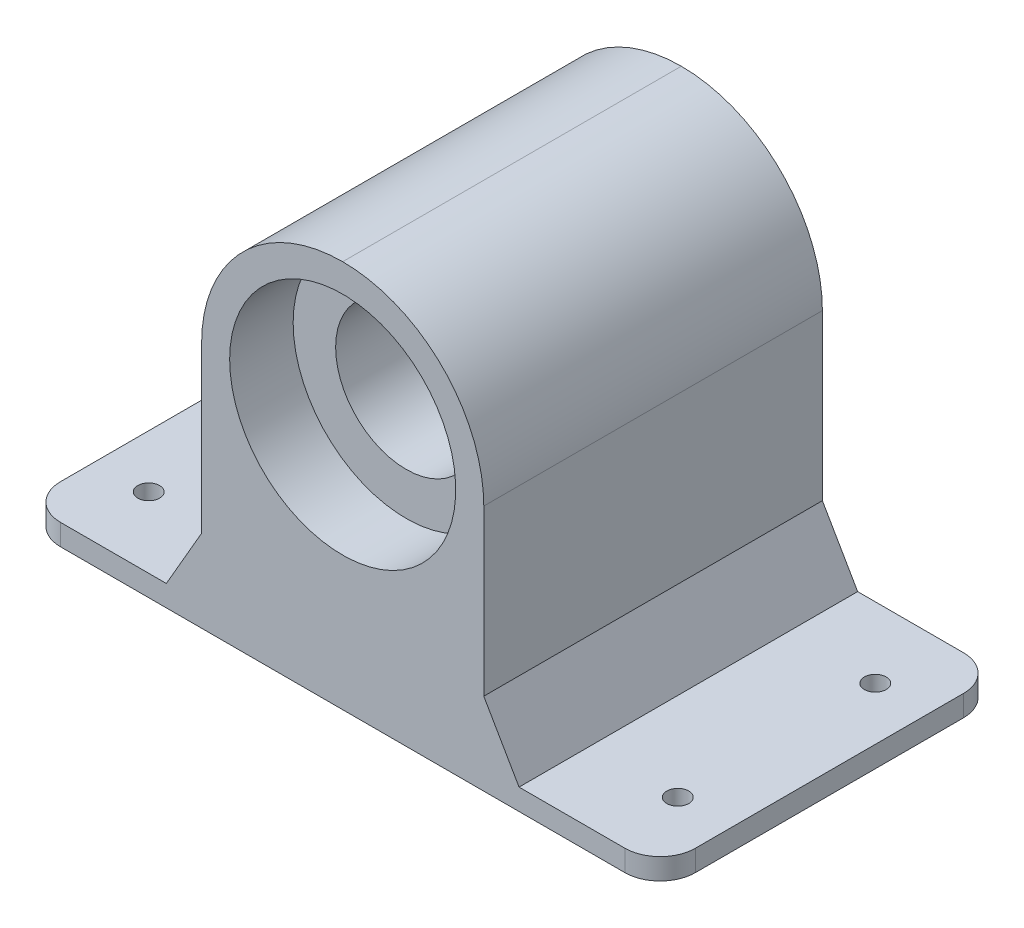
SolidWorks part; units mm, degrees
material "6061-T6 (SS)"
ref_plane "前视基准面" through (0, 0, 0) normal (0, 0, 1) x (1, 0, 0)
ref_plane "上视基准面" through (0, 0, 0) normal (0, 1, 0) x (1, 0, 0)
ref_plane "右视基准面" through (0, 0, 0) normal (1, 0, 0) x (0, 0, -1)
sketch "草图1" plane through (0, 0, 0) normal (0, 0, 1) x (1, 0, 0)
  line L0 (-20, -35) -> (-20, 0)
  line L2 (20, 0) -> (-20, 0) construction
  line L3 (-20, -35) -> (20, -35)
  line L4 (20, 0) -> (20, 20)
  line L5 (20, 20) -> (-20, 20)
  line L6 (-20, 0) -> (-20, 20)
  line L7 (20, -35) -> (20, 0)
  circle A1 centre (0, 0) radius 10
  dimension "D2" = 20
  dimension "D3" = 40
  dimension "D4" = 20
  dimension "D1" = 35
extrude "凸台-拉伸1" add sketch "草图1" along normal mid plane 48
sketch "草图4" plane through (0, 0, -24) normal (0, 0, -1) x (-1, 0, 0)
  circle A0 centre (0, 0) radius 16.025
  dimension "D1" = 32.05
extrude "切除-拉伸3" cut sketch "草图4" against normal blind 9
mirror "镜向1" about plane through (0, 0, 0) normal (0, 0, 1) of "切除-拉伸3"
ref_plane "基准面1" through (0, 0, 0) normal (-1, 0, 0) x (0, 0, 1)
sketch "草图5" plane through (20, 0, 0) normal (1, 0, 0) x (0, 0, -1)
  line L0 (24, -35) -> (24, 20) construction
  line L1 (-24, -35) -> (24, -35)
  line L2 (-24, -35) -> (-24, -32)
  line L3 (-24, -32) -> (24, -32)
  line L4 (24, -35) -> (24, -32)
  dimension "D1" = 3
extrude "凸台-拉伸2" add sketch "草图5" along normal blind 25
mirror "镜向2" about plane through (0, 0, 0) normal (-1, 0, 0) of "凸台-拉伸2"
chamfer "倒角1" distance 5 angle 60 2 edges at (-20, -32, 0) (20, -32, 0) first distance on face at (-32.5, -32, 0) first distance on face at (32.5, -32, 0)
sketch "草图7" plane through (0, -35, 0) normal (0, -1, 0) x (1, 0, 0)
  line L0 (37.5, 24) -> (37.5, -24) construction
  line L1 (-45, 24) -> (45, 24) construction
  line L2 (-45, -24) -> (45, -24) construction
  line L3 (0, 24) -> (0, -24) construction
  line L4 (45, 24) -> (45, -24) construction
  line L5 (-45, 0) -> (45, 0) construction
  line L6 (-45, 24) -> (-45, -24) construction
  circle A0 centre (37.5, 14) radius 1.55
  circle A1 centre (37.5, -14) radius 1.55
  circle A2 centre (-37.5, 14) radius 1.55
  circle A3 centre (-37.5, -14) radius 1.55
  dimension "D2" = 10
  dimension "D3" = 3.1
  dimension "D1" = 7.5
extrude "切除-拉伸4" cut sketch "草图7" against normal through all
fillet "圆角1" radius 20 2 edges at (20, 20, 0) (-20, 20, 0)
fillet "圆角2" radius 5 4 edges at (45, -33.5, 24) (45, -33.5, -24) (-45, -33.5, -24) (-45, -33.5, 24)
